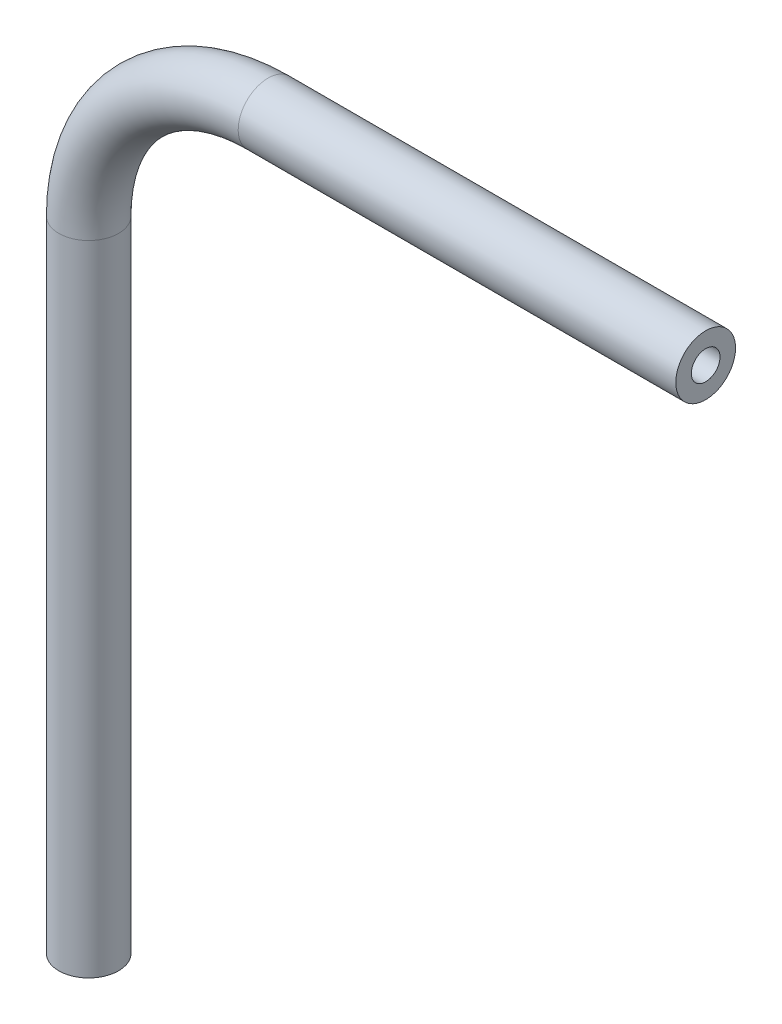
SolidWorks part; units mm, degrees
material "6061 Alloy"
ref_plane "Front Plane" through (0, 0, 0) normal (0, 0, 1) x (1, 0, 0)
ref_plane "Top Plane" through (0, 0, 0) normal (0, 1, 0) x (1, 0, 0)
ref_plane "Right Plane" through (0, 0, 0) normal (1, 0, 0) x (0, 0, -1)
sketch "Sketch1" plane through (0, 0, 0) normal (0, 0, 1) x (1, 0, 0)
  line L0 (0, -69.3403) -> (0, -1.5223)
  line L1 (19.05, 17.5277) -> (65.5179, 17.5277)
  arc A0 (0, -1.5223) -> (19.05, 17.5277) centre (19.05, -1.5223) cw
  point P6 (0, 17.5277)
  dimension "D3" = 19.05
  dimension "D1" = 65.5179
  dimension "D2" = 86.868
  dimension "D4" = 90
ref_plane "Plane1" through (65.5179, 17.5277, 0) normal (1, 0, 0) x (0, 0, -1)
sketch "Sketch2" plane through (65.5179, 17.5277, 0) normal (1, 0, 0) x (0, 0, -1)
  circle A0 centre (0, 0) radius 3.175
  circle A1 centre (0, 0) radius 1.524
  dimension "D1" = 6.35
  dimension "D2" = 3.048
sweep "Sweep1" add profiles "Sketch2" path "Sketch1"
